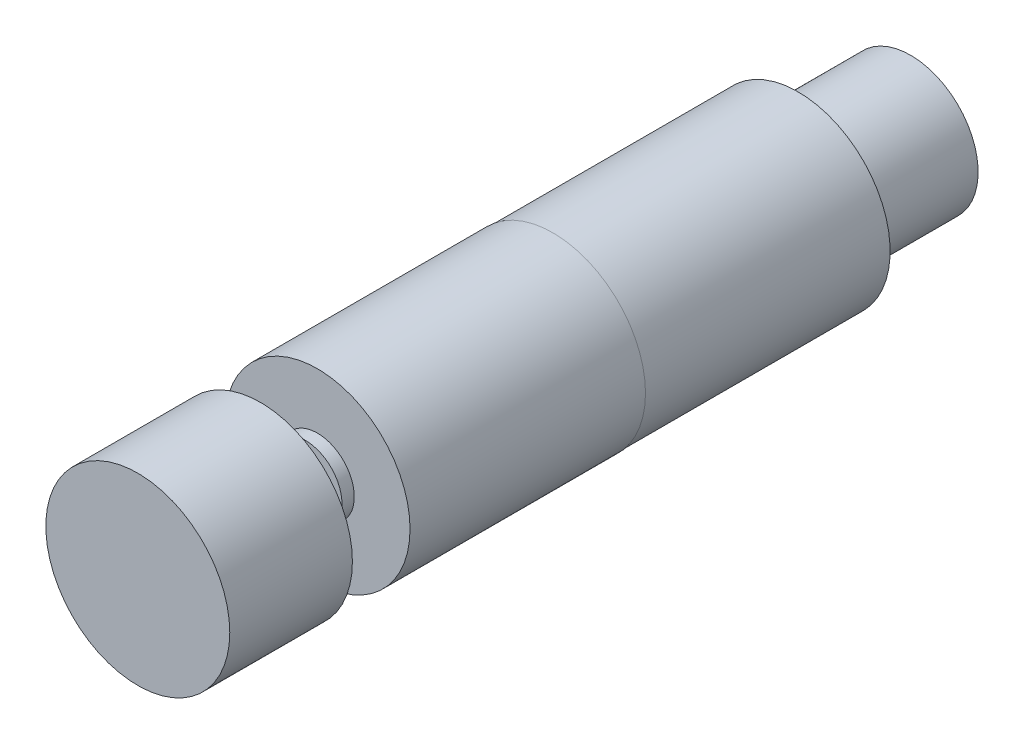
SolidWorks part; units mm, degrees
ref_plane "Front Plane" through (0, 0, 0) normal (0, 0, 1) x (1, 0, 0)
ref_plane "Top Plane" through (0, 0, 0) normal (0, 1, 0) x (1, 0, 0)
ref_plane "Right Plane" through (0, 0, 0) normal (1, 0, 0) x (0, 0, -1)
sketch "Sketch1" plane through (0, 0, 0) normal (0, 0, 1) x (1, 0, 0)
  circle A0 centre (0, 0) radius 15.1
extrude "Boss-Extrude1" add sketch "Sketch1" along normal blind 38.4 contours A0
sketch "Sketch2" plane through (0, 0, 0) normal (0, 0, -1) x (-1, 0, 0)
  circle A0 centre (0, 0) radius 15
extrude "Boss-Extrude2" add sketch "Sketch2" along normal blind 40 separate body
sketch "Sketch3" plane through (0, 0, 38.4) normal (0, 0, 1) x (1, 0, 0)
  circle A0 centre (0, 0) radius 6
extrude "Boss-Extrude3" add sketch "Sketch3" along normal blind 2 contours A0
sketch "Sketch4" plane through (0, 0, -40) normal (0, 0, -1) x (-1, 0, 0)
  circle A0 centre (0, 0) radius 11
extrude "Boss-Extrude4" add sketch "Sketch4" along normal blind 18.35 separate body contours A0
sketch "Sketch5" plane through (0, 0, 40.4) normal (0, 0, 1) x (1, 0, 0)
  circle A0 centre (0, 0) radius 3
extrude "Boss-Extrude5" add sketch "Sketch5" along normal blind 17.3 separate body contours A0
sketch "Sketch6" plane through (0, 0, 57.7) normal (0, 0, 1) x (1, 0, 0)
  circle A0 centre (0, 0) radius 15
extrude "Boss-Extrude6" add sketch "Sketch6" against normal blind 10 and the other way blind 10 contours A0
